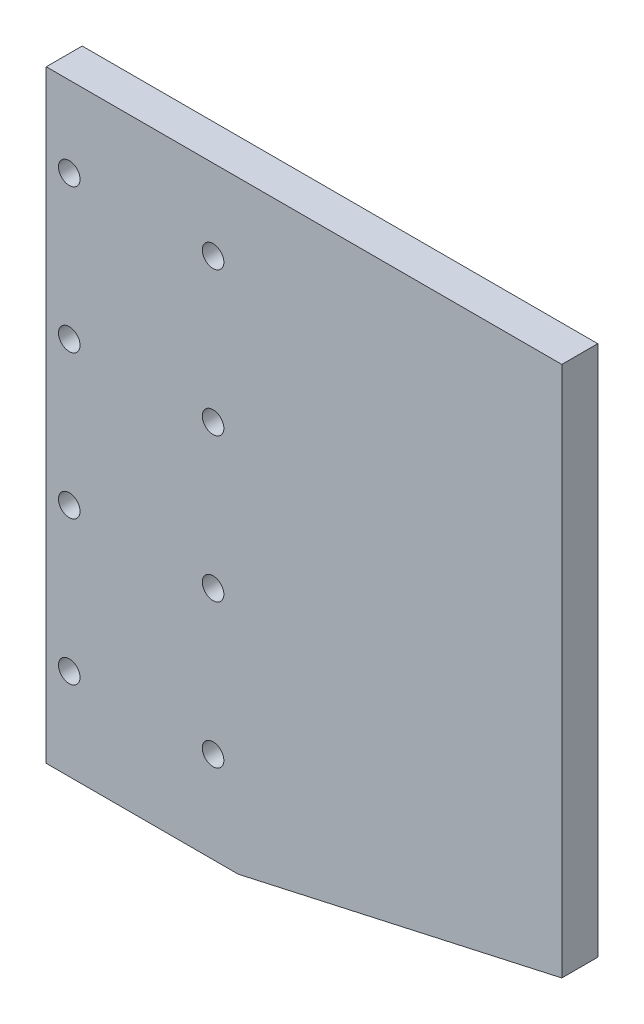
SolidWorks part; units mm, degrees
ref_plane "Front Plane" through (0, 0, 0) normal (0, 0, 1) x (1, 0, 0)
ref_plane "Top Plane" through (0, 0, 0) normal (0, 1, 0) x (1, 0, 0)
ref_plane "Right Plane" through (0, 0, 0) normal (1, 0, 0) x (0, 0, -1)
sketch "Sketch2" plane through (0, 0, 0) normal (0, 0, 1) x (1, 0, 0)
  line L0 (-12.6, -22.7) -> (-13.2, -22.7)
  line L1 (13.5, 16.2) -> (-13.5, 16.2)
  line L2 (13.5, 16.2) -> (13.5, -16.2)
  line L3 (13.5, -16.2) -> (-13.5, -16.2)
  line L4 (-13.5, 16.2) -> (-13.5, -16.2)
  line L5 (-12.6, -22.7) -> (-13.2, -22.7)
  line L6 (-13.2, -22.7) -> (-13.2, -21.2)
  line L7 (-13.2, -22.7) -> (-13.2, -21.2)
  line L8 (-13.2, -21.2) -> (-13.2, -16.2)
  line L9 (-13.2, -21.2) -> (-13.2, -16.2)
  line L10 (-13.2, -16.2) -> (-13.5, -16.2)
  line L11 (-13.2, -16.2) -> (-13.5, -16.2)
  line L12 (-13.5, -16.2) -> (-13.5, 16.2)
  line L13 (-13.5, -16.2) -> (-13.5, 16.2)
  line L14 (-13.5, 16.2) -> (-13.2, 16.2)
  line L15 (-13.5, 16.2) -> (-13.2, 16.2)
  line L16 (-13.2, 16.2) -> (-13.2, 21.2)
  line L17 (-13.2, 16.2) -> (-13.2, 21.2)
  line L18 (-13.2, 21.2) -> (-13.2, 22.7)
  line L19 (-13.2, 21.2) -> (-13.2, 22.7)
  line L20 (-13.2, 22.7) -> (-12.6, 22.7)
  line L21 (-13.2, 22.7) -> (-12.6, 22.7)
  line L22 (-12.6, 22.7) -> (-7.6219, 22.7)
  line L23 (-12.6, 22.7) -> (-7.6219, 22.7)
  line L24 (-7.1853, 22.7846) -> (-7.1541, 22.7881)
  line L25 (-7.1853, 22.7846) -> (-7.1541, 22.7881)
  line L26 (-7.1541, 22.7881) -> (-7.1541, 22.7474)
  line L27 (-7.1541, 22.7881) -> (-7.1541, 22.7474)
  line L28 (-7.1541, 22.7474) -> (-6.9151, 22.7881)
  line L29 (-7.1541, 22.7474) -> (-6.9151, 22.7881)
  line L30 (-6.9151, 22.7881) -> (-6.9, 22.786)
  line L31 (-6.9151, 22.7881) -> (-6.9, 22.786)
  line L32 (-6.9, 22.786) -> (-6.8849, 22.7881)
  line L33 (-6.9, 22.786) -> (-6.8849, 22.7881)
  line L34 (-6.8849, 22.7881) -> (-6.6459, 22.7474)
  line L35 (-6.8849, 22.7881) -> (-6.6459, 22.7474)
  line L36 (-6.6459, 22.7474) -> (-6.6459, 22.7881)
  line L37 (-6.6459, 22.7474) -> (-6.6459, 22.7881)
  line L38 (-6.6459, 22.7881) -> (-6.6146, 22.7846)
  line L39 (-6.6459, 22.7881) -> (-6.6146, 22.7846)
  line L40 (-6.1803, 22.7) -> (-6, 22.7)
  line L41 (-6.1803, 22.7) -> (-6, 22.7)
  line L42 (-6, 22.7) -> (-5.8448, 22.7)
  line L43 (-6, 22.7) -> (-5.8448, 22.7)
  line L44 (-5.8448, 22.7) -> (-5.2672, 22.7)
  line L45 (-5.8448, 22.7) -> (-5.2672, 22.7)
  line L46 (-5.2672, 22.7) -> (-5.0738, 22.7)
  line L47 (-5.2672, 22.7) -> (-5.0738, 22.7)
  line L48 (-5.0738, 22.7) -> (-4.7282, 22.7)
  line L49 (-5.0738, 22.7) -> (-4.7282, 22.7)
  line L50 (-4.7282, 22.7) -> (-4.5, 22.7)
  line L51 (-4.7282, 22.7) -> (-4.5, 22.7)
  line L52 (-4.5, 22.7) -> (4.5, 22.7)
  line L53 (-4.5, 22.7) -> (4.5, 22.7)
  line L54 (4.5, 22.7) -> (4.7282, 22.7)
  line L55 (4.5, 22.7) -> (4.7282, 22.7)
  line L56 (4.7282, 22.7) -> (5.0738, 22.7)
  line L57 (4.7282, 22.7) -> (5.0738, 22.7)
  line L58 (5.0738, 22.7) -> (5.2672, 22.7)
  line L59 (5.0738, 22.7) -> (5.2672, 22.7)
  line L60 (5.2672, 22.7) -> (5.8448, 22.7)
  line L61 (5.2672, 22.7) -> (5.8448, 22.7)
  line L62 (5.8448, 22.7) -> (6, 22.7)
  line L63 (5.8448, 22.7) -> (6, 22.7)
  line L64 (6, 22.7) -> (6.1763, 22.7)
  line L65 (6, 22.7) -> (6.1763, 22.7)
  line L66 (6.6107, 22.7846) -> (6.6459, 22.7881)
  line L67 (6.6107, 22.7846) -> (6.6459, 22.7881)
  line L68 (6.6459, 22.7881) -> (6.6459, 22.7474)
  line L69 (6.6459, 22.7881) -> (6.6459, 22.7474)
  line L70 (6.6459, 22.7474) -> (6.8849, 22.7881)
  line L71 (6.6459, 22.7474) -> (6.8849, 22.7881)
  line L72 (6.8849, 22.7881) -> (6.9, 22.7864)
  line L73 (6.8849, 22.7881) -> (6.9, 22.7864)
  line L74 (6.9, 22.7864) -> (6.9151, 22.7881)
  line L75 (6.9, 22.7864) -> (6.9151, 22.7881)
  line L76 (6.9151, 22.7881) -> (7.1541, 22.7476)
  line L77 (6.9151, 22.7881) -> (7.1541, 22.7476)
  line L78 (7.1541, 22.7476) -> (7.1541, 22.7881)
  line L79 (7.1541, 22.7476) -> (7.1541, 22.7881)
  line L80 (7.1541, 22.7881) -> (7.1893, 22.7846)
  line L81 (7.1541, 22.7881) -> (7.1893, 22.7846)
  line L82 (7.6199, 22.7) -> (12.6, 22.7)
  line L83 (7.6199, 22.7) -> (12.6, 22.7)
  line L84 (12.6, 22.7) -> (13.2, 22.7)
  line L85 (12.6, 22.7) -> (13.2, 22.7)
  line L86 (13.2, 22.7) -> (13.2, 21.2)
  line L87 (13.2, 22.7) -> (13.2, 21.2)
  line L88 (13.2, 21.2) -> (13.2, 16.2)
  line L89 (13.2, 21.2) -> (13.2, 16.2)
  line L90 (13.2, 16.2) -> (13.5, 16.2)
  line L91 (13.2, 16.2) -> (13.5, 16.2)
  line L92 (13.5, 16.2) -> (13.5, -16.2)
  line L93 (13.5, 16.2) -> (13.5, -16.2)
  line L94 (13.5, -16.2) -> (13.2, -16.2)
  line L95 (13.5, -16.2) -> (13.2, -16.2)
  line L96 (13.2, -16.2) -> (13.2, -21.2)
  line L97 (13.2, -16.2) -> (13.2, -21.2)
  line L98 (13.2, -21.2) -> (13.2, -22.7)
  line L99 (13.2, -21.2) -> (13.2, -22.7)
  line L100 (13.2, -22.7) -> (12.6, -22.7)
  line L101 (13.2, -22.7) -> (12.6, -22.7)
  line L102 (12.6, -22.7) -> (7.6219, -22.7)
  line L103 (12.6, -22.7) -> (7.6219, -22.7)
  line L104 (7.1853, -22.7846) -> (7.1541, -22.7881)
  line L105 (7.1853, -22.7846) -> (7.1541, -22.7881)
  line L106 (7.1541, -22.7881) -> (7.1541, -22.7474)
  line L107 (7.1541, -22.7881) -> (7.1541, -22.7474)
  line L108 (7.1541, -22.7474) -> (6.9151, -22.7881)
  line L109 (7.1541, -22.7474) -> (6.9151, -22.7881)
  line L110 (6.9151, -22.7881) -> (6.9, -22.786)
  line L111 (6.9151, -22.7881) -> (6.9, -22.786)
  line L112 (6.9, -22.786) -> (6.8849, -22.7881)
  line L113 (6.9, -22.786) -> (6.8849, -22.7881)
  line L114 (6.8849, -22.7881) -> (6.6459, -22.7474)
  line L115 (6.8849, -22.7881) -> (6.6459, -22.7474)
  line L116 (6.6459, -22.7474) -> (6.6459, -22.7881)
  line L117 (6.6459, -22.7474) -> (6.6459, -22.7881)
  line L118 (6.6459, -22.7881) -> (6.6146, -22.7846)
  line L119 (6.6459, -22.7881) -> (6.6146, -22.7846)
  line L120 (6.1803, -22.7) -> (6, -22.7)
  line L121 (6.1803, -22.7) -> (6, -22.7)
  line L122 (6, -22.7) -> (5.8448, -22.7)
  line L123 (6, -22.7) -> (5.8448, -22.7)
  line L124 (5.8448, -22.7) -> (5.2672, -22.7)
  line L125 (5.8448, -22.7) -> (5.2672, -22.7)
  line L126 (5.2672, -22.7) -> (5.0738, -22.7)
  line L127 (5.2672, -22.7) -> (5.0738, -22.7)
  line L128 (5.0738, -22.7) -> (4.7282, -22.7)
  line L129 (5.0738, -22.7) -> (4.7282, -22.7)
  line L130 (4.7282, -22.7) -> (4.5, -22.7)
  line L131 (4.7282, -22.7) -> (4.5, -22.7)
  line L132 (4.5, -22.7) -> (-4.5, -22.7)
  line L133 (4.5, -22.7) -> (-4.5, -22.7)
  line L134 (-4.5, -22.7) -> (-4.7282, -22.7)
  line L135 (-4.5, -22.7) -> (-4.7282, -22.7)
  line L136 (-4.7282, -22.7) -> (-5.0738, -22.7)
  line L137 (-4.7282, -22.7) -> (-5.0738, -22.7)
  line L138 (-5.0738, -22.7) -> (-5.2672, -22.7)
  line L139 (-5.0738, -22.7) -> (-5.2672, -22.7)
  line L140 (-5.2672, -22.7) -> (-5.8448, -22.7)
  line L141 (-5.2672, -22.7) -> (-5.8448, -22.7)
  line L142 (-5.8448, -22.7) -> (-6, -22.7)
  line L143 (-5.8448, -22.7) -> (-6, -22.7)
  line L144 (-6, -22.7) -> (-6.1763, -22.7)
  line L145 (-6, -22.7) -> (-6.1763, -22.7)
  line L146 (-6.6107, -22.7846) -> (-6.6459, -22.7881)
  line L147 (-6.6107, -22.7846) -> (-6.6459, -22.7881)
  line L148 (-6.6459, -22.7881) -> (-6.6459, -22.7474)
  line L149 (-6.6459, -22.7881) -> (-6.6459, -22.7474)
  line L150 (-6.6459, -22.7474) -> (-6.8849, -22.7881)
  line L151 (-6.6459, -22.7474) -> (-6.8849, -22.7881)
  line L152 (-6.8849, -22.7881) -> (-6.9, -22.7864)
  line L153 (-6.8849, -22.7881) -> (-6.9, -22.7864)
  line L154 (-6.9, -22.7864) -> (-6.9151, -22.7881)
  line L155 (-6.9, -22.7864) -> (-6.9151, -22.7881)
  line L156 (-6.9151, -22.7881) -> (-7.1541, -22.7476)
  line L157 (-6.9151, -22.7881) -> (-7.1541, -22.7476)
  line L158 (-7.1541, -22.7476) -> (-7.1541, -22.7881)
  line L159 (-7.1541, -22.7476) -> (-7.1541, -22.7881)
  line L160 (-7.1541, -22.7881) -> (-7.1893, -22.7846)
  line L161 (-7.1541, -22.7881) -> (-7.1893, -22.7846)
  line L162 (-7.6199, -22.7) -> (-12.6, -22.7)
  line L163 (-7.6199, -22.7) -> (-12.6, -22.7)
  line L164 (13.2, 21.2) -> (13.5, 21.2)
  line L165 (13.2, 21.2) -> (-13.2, 21.2)
  line L166 (13.2, 21.2) -> (13.2, -21.2)
  line L167 (13.2, -21.2) -> (-13.2, -21.2)
  line L168 (-13.2, 21.2) -> (-13.2, -21.2)
  line L169 (13.5, 21.2) -> (13.5, 16.2)
  line L170 (13.5, -16.2) -> (13.5, -21.2)
  line L171 (13.5, -21.2) -> (13.2, -21.2)
  circle A0 centre (10, 10) radius 1.5
  circle A1 centre (10, -10) radius 1.5
  circle A2 centre (-10, -10) radius 1.5
  circle A3 centre (-10, 10) radius 1.5
  spline S0 degree 3 poles (-797.1844, 3943.7501) (-14.9658, -50.0095) (-18.4177, 20.8864) (1.827, 24.3127) (16.3324, -1.4834) (-762.3248, 3950.5803) knots -75.033523 -75.033523 -75.033523 -75.033523 0.5 0.75 63.364271 63.364271 63.364271 63.364271 only from (-7.6219, 22.7) to (-7.1853, 22.7846)
  spline S1 degree 3 poles (-7.6219, 22.7) (-7.5501, 22.7187) (-7.4418, 22.744) (-7.2956, 22.7688) (-7.2221, 22.7794) (-7.1853, 22.7846) knots 0 0 0 0 0.5 0.75 1 1 1 1
  spline S2 degree 3 poles (826.9263, 3934.7279) (-33.2558, -17.5729) (-15.2021, 24.6103) (1.3651, 21.1114) (1.7287, -14.3882) (862.4754, 3927.0421) knots -60.76662 -60.76662 -60.76662 -60.76662 0.5 0.75 54.022648 54.022648 54.022648 54.022648 only from (-6.6146, 22.7846) to (-6.1803, 22.7)
  spline S3 degree 3 poles (-6.6146, 22.7846) (-6.5414, 22.7744) (-6.4318, 22.7581) (-6.2875, 22.7276) (-6.216, 22.7094) (-6.1803, 22.7) knots 0 0 0 0 0.5 0.75 1 1 1 1
  spline S4 degree 3 poles (-707.7305, 3958.2219) (-8.2936, -42.4412) (-5.6397, 80.3515) (43.1185, -27.7595) (-782.9005, 3943.7687) knots -91.570916 -91.570916 -91.570916 -91.570916 0.5 89.04511 89.04511 89.04511 89.04511 only from (6.1763, 22.7) to (6.6107, 22.7846)
  spline S5 degree 3 poles (6.1763, 22.7) (6.2481, 22.717) (6.3922, 22.7487) (6.5378, 22.7733) (6.6107, 22.7846) knots 0 0 0 0 0.5 1 1 1 1
  spline S6 degree 3 poles (761.1024, 3950.9) (-20.4451, -24.9532) (-1.4009, 24.7075) (16.2108, 20.7945) (19.0505, -9.9841) (809.174, 3941.3306) knots -61.399365 -61.399365 -61.399365 -61.399365 0.5 0.75 61.881222 61.881222 61.881222 61.881222 only from (7.1893, 22.7846) to (7.6199, 22.7)
  spline S7 degree 3 poles (7.1893, 22.7846) (7.2619, 22.7749) (7.3706, 22.7586) (7.5134, 22.7269) (7.5845, 22.7091) (7.6199, 22.7) knots 0 0 0 0 0.5 0.75 1 1 1 1
  spline S8 degree 3 poles (797.1844, -3943.7501) (14.9658, 50.0095) (18.4177, -20.8864) (-1.827, -24.3127) (-16.3324, 1.4834) (762.3248, -3950.5803) knots -75.033523 -75.033523 -75.033523 -75.033523 0.5 0.75 63.364271 63.364271 63.364271 63.364271 only from (7.6219, -22.7) to (7.1853, -22.7846)
  spline S9 degree 3 poles (7.6219, -22.7) (7.5501, -22.7187) (7.4418, -22.744) (7.2956, -22.7688) (7.2221, -22.7794) (7.1853, -22.7846) knots 0 0 0 0 0.5 0.75 1 1 1 1
  spline S10 degree 3 poles (-826.9263, -3934.7279) (33.2558, 17.5729) (15.2021, -24.6103) (-1.3651, -21.1114) (-1.7287, 14.3882) (-862.4754, -3927.0421) knots -60.76662 -60.76662 -60.76662 -60.76662 0.5 0.75 54.022648 54.022648 54.022648 54.022648 only from (6.6146, -22.7846) to (6.1803, -22.7)
  spline S11 degree 3 poles (6.6146, -22.7846) (6.5414, -22.7744) (6.4318, -22.7581) (6.2875, -22.7276) (6.216, -22.7094) (6.1803, -22.7) knots 0 0 0 0 0.5 0.75 1 1 1 1
  spline S12 degree 3 poles (707.7305, -3958.2219) (8.2936, 42.4412) (5.6397, -80.3515) (-43.1185, 27.7595) (782.9005, -3943.7687) knots -91.570916 -91.570916 -91.570916 -91.570916 0.5 89.04511 89.04511 89.04511 89.04511 only from (-6.1763, -22.7) to (-6.6107, -22.7846)
  spline S13 degree 3 poles (-6.1763, -22.7) (-6.2481, -22.717) (-6.3922, -22.7487) (-6.5378, -22.7733) (-6.6107, -22.7846) knots 0 0 0 0 0.5 1 1 1 1
  spline S14 degree 3 poles (-761.0726, -3950.8048) (20.444, 24.9514) (1.4006, -24.7074) (-16.2103, -20.7946) (-19.0492, 9.9846) (-809.2031, -3941.3057) knots -61.397714 -61.397714 -61.397714 -61.397714 0.5 0.75 61.877321 61.877321 61.877321 61.877321 only from (-7.1893, -22.7846) to (-7.6199, -22.7)
  spline S15 degree 3 poles (-7.1893, -22.7846) (-7.2619, -22.7749) (-7.3706, -22.7586) (-7.5134, -22.7269) (-7.5845, -22.7091) (-7.6199, -22.7) knots 0 0 0 0 0.5 0.75 1 1 1 1
  circle M5 centre (10, -10) radius 1.75
  circle M6 centre (10, 10) radius 1.75
  line M7 (12.9, 16.2) -> (6.4, 16.2)
  line M8 (6.4, 16.2) -> (6.4, -16.2)
  line M9 (6.4, -16.2) -> (12.9, -16.2)
  line M10 (12.9, -16.2) -> (12.9, 16.2)
  dimension "D1" = 3
  dimension "D2" = 3
  dimension "D3" = 3
  dimension "D4" = 3
extrude "Boss-Extrude1" add sketch "Sketch2" along normal blind 5 contours L1 L168 L3 A3 A2 M8 | M10 M7 M8 M9 M6 M5 | L167 L97 L3 L9 M9 | L171 L170 L3 L97 | L1 L166 L3 L2 | L166 L1 L3 M10 | L89 L165 L17 L1 M7 | L169 L164 L89 L1 | A0 M6 | A1 M5 region at (0, -18.7, 0) region at (-3.2497, 0, 0) region at (13.35, -18.7, 0) region at (9.6148, 0, 0) region at (0, 18.7, 0) region at (13.35, 0, 0) region at (13.05, 0, 0) region at (13.35, 18.7, 0) region at (8.2995, -10, 0) region at (8.2995, 10, 0)
sketch "Sketch3" plane through (0, 0, 5) normal (0, 0, 1) x (1, 0, 0)
  line L1 (13.5, -62.7) -> (13.5, -21.2)
  line L2 (13.5, -21.2) -> (-13.2, -21.2)
  line L3 (-13.2, -21.2) -> (-13.2, -62.7)
  line L4 (-13.2, -62.7) -> (13.5, -62.7)
extrude "Boss-Extrude2" add sketch "Sketch3" against normal blind 5
sketch "Sketch4" plane through (0, 0, 5) normal (0, 0, 1) x (1, 0, 0)
  circle A0 centre (10, 17.2502) radius 1.5 construction
  circle A1 centre (10, -10) radius 1.5 construction
  circle A2 centre (10, -10) radius 1.5
  circle A3 centre (-10, -10) radius 1.5
  circle A4 centre (-10, -30) radius 1.5
  circle A5 centre (10, -30) radius 1.5
  circle A6 centre (-10, -50) radius 1.5
  circle A7 centre (10, -50) radius 1.5
  dimension "D1" = 27.2502
  dimension "D2" = 3
  dimension "D3" = 3
  dimension "D4" = 3
extrude "Cut-Extrude1" cut sketch "Sketch4" against normal blind 5
sketch "Sketch5" plane through (0, 0, 5) normal (0, 0, 1) x (1, 0, 0)
  line L0 (13.5, -62.7) -> (58.5, -52.7)
  line L1 (13.5, 21.2) -> (58.5, 21.2)
  line L2 (58.5, 21.2) -> (58.5, -52.7)
  line L3 (13.5, -62.7) -> (13.5, 21.2)
  line L4 (40.5, -41.7116) -> (40.5, -62.7)
  line L5 (40.5, -62.7) -> (40.5, 24.3033)
extrude "Boss-Extrude3" add sketch "Sketch5" against normal blind 5 region at (26.8331, -19.2685, 5)
extrude "Boss-Extrude4" add sketch "Sketch5<3>" against normal up to surface (5 mm away) contours L0 L2 L1 region at (49.4209, -16.7588, 5)
sketch "Sketch5<3>" plane through (0, 0, 5) normal (0, 0, 1) x (1, 0, 0) same geometry as "Sketch5"
